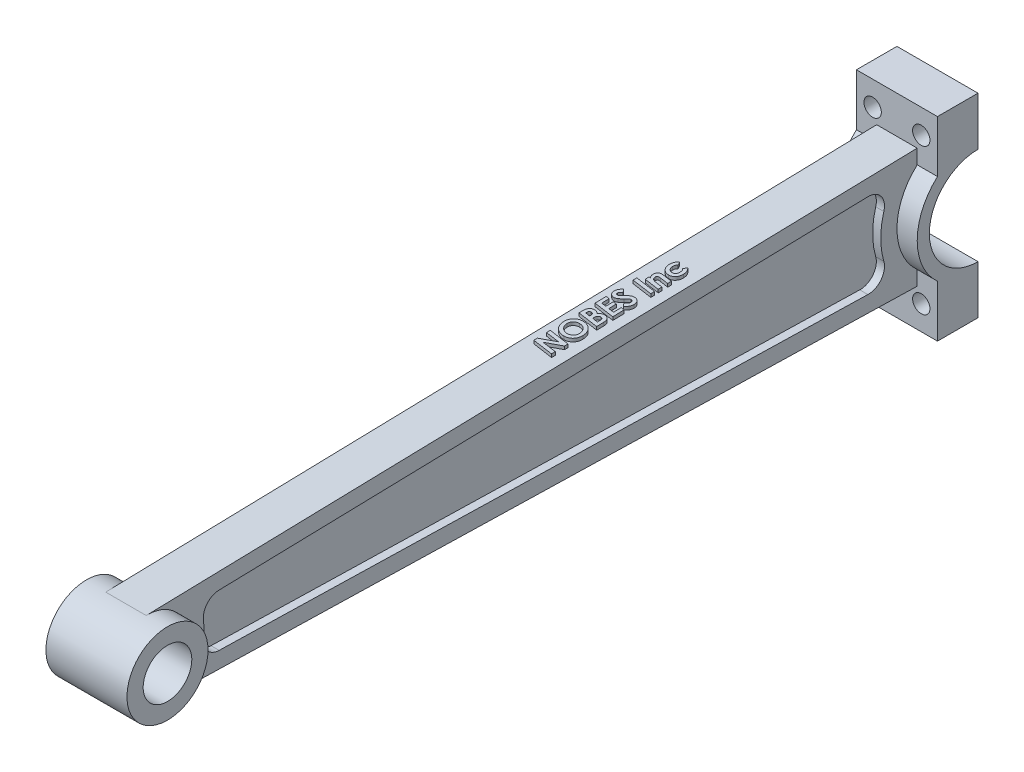
SolidWorks part; units mm, degrees
material "Cast Alloy Steel"
ref_plane "Front Plane" through (0, 0, 0) normal (0, 0, 1) x (1, 0, 0)
ref_plane "Top Plane" through (0, 0, 0) normal (0, 1, 0) x (1, 0, 0)
ref_plane "Right Plane" through (0, 0, 0) normal (1, 0, 0) x (0, 0, -1)
sketch "Sketch1" plane through (0, 0, 0) normal (1, 0, 0) x (0, 0, -1)
  line L0 (-25, 27.9508) -> (-25, 60)
  line L1 (-25, 60) -> (0, 60)
  line L2 (0, 60) -> (0, 30)
  line L3 (0, -30) -> (0, -60)
  line L4 (0, -60) -> (-25, -60)
  line L5 (-25, -60) -> (-25, -27.9508)
  arc A0 (-25, 27.9508) -> (-25, -27.9508) centre (0, 0) ccw
  arc A2 (0, 30) -> (0, -30) centre (0, 0) ccw
  dimension "D1" = 75
  dimension "D2" = 60
  dimension "D3" = 120
  dimension "D4" = 60
  dimension "D5" = 25
extrude "Journal_Boss" add sketch "Sketch1" along normal mid plane 50
sketch "Sketch2" plane through (0, 0, 0) normal (1, 0, 0) x (0, 0, -1)
  line L0 (27.5, 0) -> (-27.5, 0) construction
  circle A0 centre (-500, 0) radius 25
  circle A1 centre (-500, 0) radius 15
  dimension "D1" = 50
  dimension "D2" = 30
  dimension "D3" = 500
extrude "Pinion_Boss" add sketch "Sketch2" along normal mid plane 50 separate body
sketch "Sketch3" plane through (0, 0, 0) normal (1, 0, 0) x (0, 0, -1)
  line L0 (-500.625, 24.9922) -> (-0.9375, 37.4883)
  line L1 (-500.625, -24.9922) -> (-0.9375, -37.4883)
  circle A0 centre (-500, 0) radius 25 construction
  arc A1 (-500.625, -24.9922) -> (-500.625, 24.9922) centre (-500, 0) ccw
  circle A2 centre (0, 0) radius 37.5 construction
  arc A3 (-0.9375, 37.4883) -> (-0.9375, -37.4883) centre (0, 0) ccw
extrude "Boss-Extrude3" add sketch "Sketch3" along normal mid plane 25
sketch "Sketch4" plane through (12.5, 0, 0) normal (1, 0, 0) x (0, 0, -1)
  line L2 (-24.75, 26.8897) -> (-500.375, 14.9953)
  line L3 (-55.4426, 26.1221) -> (-455.6676, 16.1133)
  line L5 (-468.7621, -15.7859) -> (-24.75, -26.8897)
  line L6 (-455.6676, -16.1133) -> (-55.4426, -26.1221)
  arc A3 (-468.7621, -15.7859) -> (-500.875, 34.9891) centre (-500, 0) ccw
  arc A4 (-465.3248, -4.7573) -> (-465.3248, 4.7573) centre (-500, 0) ccw
  arc A5 (-45.5939, -13.3208) -> (-55.4426, -26.1221) centre (-55.1926, -16.1252) cw
  arc A6 (-31.6667, 35.4044) -> (-31.6667, -35.4044) centre (0, 0) ccw
  arc A7 (-45.5939, 13.3208) -> (-45.5939, -13.3208) centre (0, 0) ccw
  arc A8 (-45.5939, 13.3208) -> (-55.4426, 26.1221) centre (-55.1926, 16.1252) ccw
  arc A9 (-455.6676, 16.1133) -> (-465.3248, 4.7573) centre (-455.4176, 6.1165) ccw
  arc A10 (-455.6676, -16.1133) -> (-465.3248, -4.7573) centre (-455.4176, -6.1165) cw
  dimension "D4" = 10
  dimension "D1" = 10
  dimension "D2" = 10
  dimension "D3" = 10
extrude "Cut-Extrude1" cut sketch "Sketch4" against normal blind 5
mirror "Mirror1" about plane through (0, 0, 0) normal (1, 0, 0) of "Cut-Extrude1"
hole_wizard "1/2-13 Tapped Hole1" positions "Sketch5" profile "Sketch6" tap size "1/2-13" standard "ANSI Inch" end condition up to next
sketch "Sketch5" plane through (0, 0, 0) normal (0, 0, -1) x (-1, 0, 0)
  point P0 (-15, 45)
  point P9 (15, 45)
  point P10 (15, -45)
  point P11 (-15, -45)
  dimension "D1" = 45
  dimension "D2" = 15
  dimension "D3" = 2
  dimension "D4" = 2
sketch "Sketch6" plane through (15, 45, 0) normal (1, 0, 0) x (0, 1, 0)
  line L0 (0, 0) -> (0, 25)
  line L1 (0, 25) -> (5.3581, 25)
  line L2 (5.3581, 25) -> (5.3581, 0)
  line L5 (5.3581, 0) -> (0, 0)
  line L11 (0, -6.35) -> (0, 107.95) construction
  dimension "Thru Tap Drill Dia." = 10.7163
  dimension "Thru Tap Drill Depth" = 25
cosmetic thread "Hole Thread1" parameters "D2"=12.7
cosmetic thread "Hole Thread2" parameters "D2"=12.7
cosmetic thread "Hole Thread3" parameters "D2"=12.7
cosmetic thread "Hole Thread4" parameters "D2"=12.7
ref_axis "Pinion Axis" through (25, 0, 500) along (-1, 0, 0)
sketch "Sketch7" plane through (0, 37.4883, 0.9375) normal (0, 0.9997, 0.025) x (1, 0, 0)
  line L0 (6.15, -110.9439) -> (6.15, -289.0561) construction
  line L1 (12.5, -24.07) -> (12.5, -499.8437) construction
  text T0 "NOBES Inc" font "Century Gothic" height 12.7
  point P4 (6.15, -200)
  dimension "D1" = 6.35
  dimension "D2" = 200
extrude "Boss-Extrude4" add sketch "Sketch7" along normal blind 2
